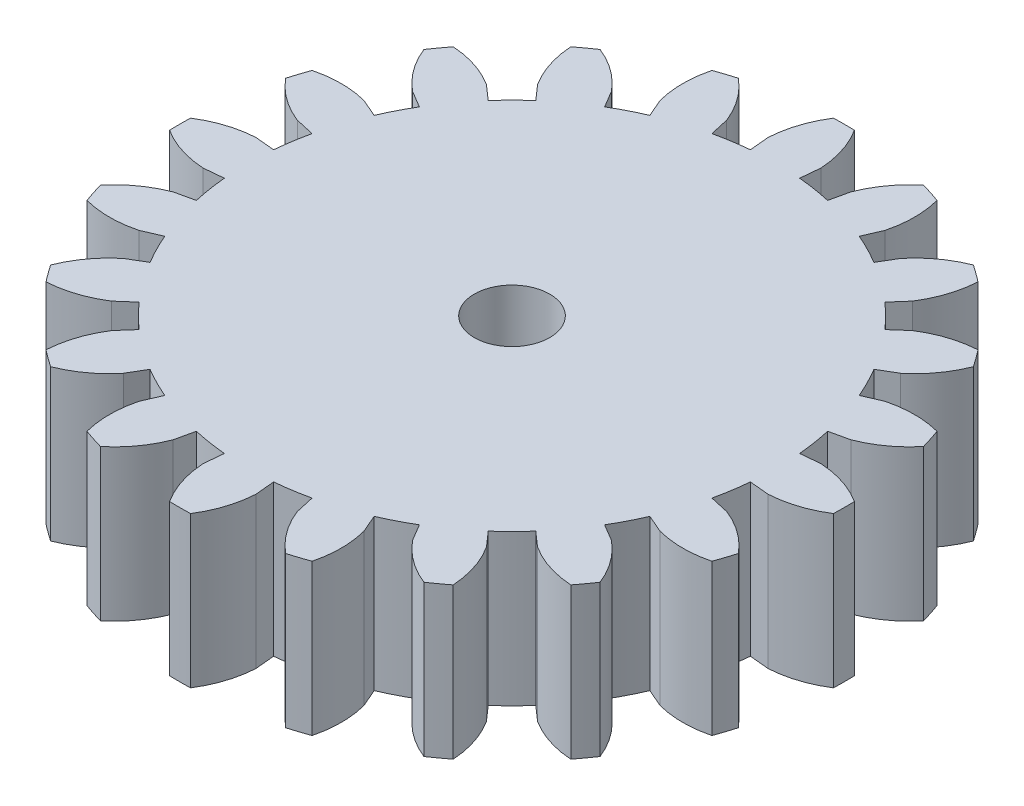
SolidWorks part; units mm, degrees
ref_plane "Спереди" through (0, 0, 0) normal (0, 0, 1) x (1, 0, 0)
ref_plane "Сверху" through (0, 0, 0) normal (0, 1, 0) x (1, 0, 0)
ref_plane "Справа" through (0, 0, 0) normal (1, 0, 0) x (0, 0, -1)
other "Configuration Table"
sketch "Эскиз1" plane through (0, 0, 0) normal (0, 1, 0) x (1, 0, 0)
  circle A0 centre (0, 0) radius 17.5
  dimension "D1" = 35
extrude "Бобышка-Вытянуть1" add sketch "Эскиз1" along normal blind 10
sketch "Эскиз2" plane through (0, 0, 0) normal (0, -1, 0) x (1, 0, 0)
  line L0 (0, 0) -> (0, 22) construction
  line L1 (0, 0) -> (-1.7523, 18.712) construction
  line L2 (0, 0) -> (1.7523, 18.712) construction
  line L5 (-1.5692, 19.9383) -> (0, 0) construction
  line L6 (0, 0) -> (1.5692, 19.9383) construction
  line L7 (-0.6949, 21.989) -> (0, 0) construction
  line L8 (-1.6317, 17.4238) -> (-1.7523, 18.712)
  line L9 (1.7523, 18.712) -> (1.6317, 17.4238)
  circle A0 centre (0, 0) radius 18.7938 construction
  circle A1 centre (0, 0) radius 20 construction
  circle A2 centre (0, 0) radius 22 construction
  arc A3 (-0.6949, 21.989) -> (0.6949, 21.989) centre (0, 0) cw
  arc A4 (-1.6317, 17.4238) -> (1.6317, 17.4238) centre (0, 0) cw
  circle A5 centre (0, 0) radius 17.5 construction
  arc A6 (-1.5692, 19.9383) -> (1.5692, 19.9383) centre (0, 0) cw construction
  arc A7 (-1.7523, 18.712) -> (-0.6949, 21.989) centre (5.0681, 18.3203) cw
  arc A8 (0.6949, 21.989) -> (1.7523, 18.712) centre (-5.0681, 18.3203) cw
  point P12 (0, 20)
  point P16 (0, 22)
  point P22 (0, 17.5)
  dimension "D1" = 37.5877
  dimension "D2" = 40
  dimension "D3" = 44
  dimension "D4" = 5.35
  dimension "D5" = 4.5
  dimension "D6" = 1.81
extrude "Бобышка-Вытянуть2" add sketch "Эскиз2" against normal blind 10
pattern_circular "Круговой массив1" count 20 over 360 about axis through (0, 10, 0) along (0, -1, 0) of "Бобышка-Вытянуть2" reverse direction yes
sketch "Эскиз3" plane through (0, 0, 0) normal (0, -1, 0) x (1, 0, 0)
  circle A0 centre (0, 0) radius 2.5
  dimension "D1" = 5
extrude "Вырез-Вытянуть1" cut sketch "Эскиз3" against normal through all
equation "\"Ширина груза\"= 420"
equation "\"Глубина груза\"= 490"
equation "\"Высота груза\"= 297"
equation "\"Ширина ячейки\"= \"Ширина груза\" + 10"
equation "\"Глубина ячейки\"= \"Глубина груза\" + 10"
equation "\"Высота ячейки\"= \"Высота груза\" + 10 + 13"
equation "\"Колво ячеек ширина\"= 2"
equation "\"Колво ячеек высота\"= 2"
equation "\"Толщина стенки\" = \"Толщина тонких панелей\""
equation "\"Крепление дверцы\"= 5 "
equation "\"Ширина рейки\"= \"Толщина шестерни\""
equation "\"Высота рейки\"= 20"
equation "\"Высота пола\" = 2*\"Толщина тонких панелей\""
equation "\"Колво полозьев\"= 5"
equation "\"Отступ рейки\"= 20"
equation "\"Глубина каретки\"= \"Глубина ячейки\" + 30 + \"Мотор Y высота корпуса\" + 20"
equation "\"Длинна рейки\" = (\"Ширина ячейки\"+\"Толщина вертикальных стенок\"+\"Крепление дверцы\")*\"Колво ячеек ширина\"+\"Ширина ячейки выгрузки\"*\"Колво выгрузки\"+\"Толщина вертикальных стенок\"+2*\"Отступ крепления мотора фиксации\"-\"Крепление дверцы\"*\"Колво ячеек ширина\""
equation "\"Отступ шпильки\"= 26"
equation "\"Диаметр шпильки\"= 5"
equation "\"Длинна шпильки\" = (\"Высота ячейки\"+\"Толщина горизонтальных плит\"+\"Высота пола\")*\"Колво ячеек высота\"+2*(\"Толщина горизонтальных плит\"+\"Отступ рейки\")"
equation "\"Ширина пластины\"= 50  "
equation "\"Высота зона выгрузки\"= \"Высота ячейки\" * 2 + \"Толщина стенки\" * 2"
equation "\"Колво выгрузки\"= 1"
equation "\"Ширина ячейки выгрузки\" = \"Ширина ячейки\"+\"Толщина вертикальных стенок\"+2*\"Отступ крепления мотора фиксации\""
equation "\"Отступ крепления мотора фиксации\" = (\"Ширина пластины\"+20-\"Толщина вертикальных стенок\")/2"
equation "\"Мотор X ширина корпуса\"= 42.3"
equation "\"Мотор X высота корпуса\"= 42.3"
equation "\"Мотор X длина корпуса\"= 40"
equation "\"Мотор X вылет вала\"= 19.8"
equation "\"Мотор Y ширина корпуса\"= 42.3"
equation "\"Мотор Y высота корпуса\"= 42.3"
equation "\"Мотор Y длина корпуса\"= 48"
equation "\"Мотор Y вылет вала\"= 30"
equation "\"Мотор Z ширина корпуса\"= 42"
equation "\"Мотор Z высота корпуса\"= 42"
equation "\"Мотор Z длина корпуса\"= 40"
equation "\"Мотор Z вылет вала\"= 23"
equation "\"Мотор диаметр вала ПРЕДВ\"= 5"
equation "\"Мотор шаг крепления ПРЕДВ\"= 31"
equation "\"Мотор диаметр отверстий ПРЕДВ\"= 3"
equation "\"Мотор глубина отверстий ПРЕДВ\"= 4.5"
equation "\"Мотор диаметр буртика ПРЕДВ\"= 22"
equation "\"Мотор высота буртика ПРЕДВ\"= 2"
equation "\"Мотор диаметр шкива ПРЕДВ\"= 16"
equation "\"Мотор длина шкива ПРЕДВ\"= 12"
equation "\"Мотор отступ шкива ПРЕДВ\"= 5"
equation "\"Мотор X шаг градусов\"= 1.8"
equation "\"Мотор Y шаг градусов\"= 1.8"
equation "\"Мотор Z шаг градусов\"= 1.8"
equation "\"Мотор Y диаметр ротора\"= 25.78"
equation "\"Толщина шестерни\"= 10"
equation "\"D1@Бобышка-Вытянуть1\"=\"Толщина шестерни\""
equation "\"D1@Бобышка-Вытянуть2\"=\"Толщина шестерни\""
equation "\"D1@Эскиз3\"=\"Мотор диаметр вала ПРЕДВ\""
equation "\"Толщина тонких панелей\"= 6"
equation "\"Толщина вертикальных стенок\"= 18"
equation "\"Толщина горизонтальных плит\"= 18"
equation "\"Базовая высота корпуса\"= (\"Высота ячейки\"+\"Толщина тонких панелей\"+\"Высота пола\")*\"Колво ячеек высота\"+6*\"Толщина тонких панелей\"+\"Мотор X ширина корпуса\"+\"Мотор Y ширина корпуса\"+75"
equation "\"Высота корпуса\"= (\"Высота ячейки\"+\"Толщина горизонтальных плит\"+\"Высота пола\")*\"Колво ячеек высота\"+2*\"Толщина горизонтальных плит\"+4*\"Толщина тонких панелей\"+\"Мотор X ширина корпуса\"+\"Мотор Y ширина корпуса\"+75"
equation "\"Смещение центра корпуса\"= (\"Высота корпуса\"-\"Базовая высота корпуса\")/2-(\"Толщина горизонтальных плит\"-\"Толщина тонких панелей\")"
equation "\"Отметка пола\"= -\"Базовая высота корпуса\"/2+\"Толщина тонких панелей\""
equation "\"Отметка потолка\"= \"Отметка пола\"+\"Высота корпуса\"-2*\"Толщина горизонтальных плит\""
equation "\"Отметка верхней полки\"= \"Отметка потолка\"-(28+\"Толщина тонких панелей\")-\"Высота ячейки\"-\"Высота пола\""
equation "\"Отметка нижней полки\"= \"Отметка верхней полки\"-\"Высота ячейки\"-\"Высота пола\"-\"Толщина горизонтальных плит\""
